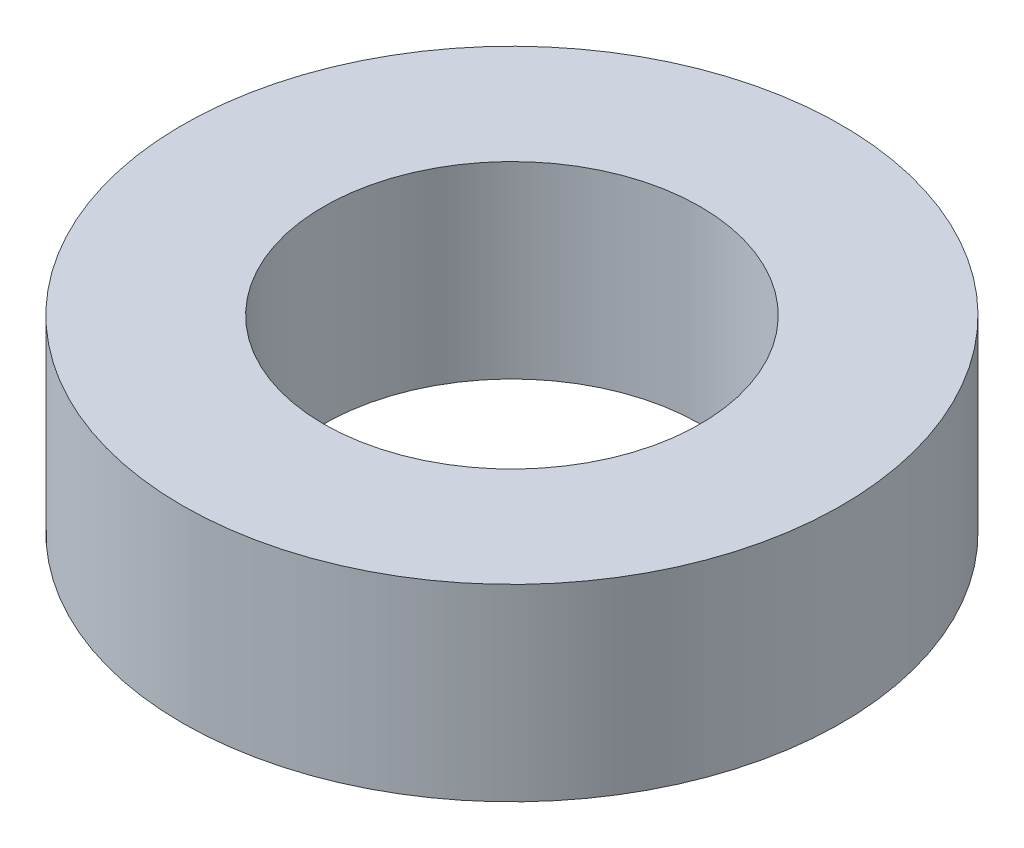
SolidWorks part; units mm, degrees
ref_plane "Front Plane" through (0, 0, 0) normal (0, 0, 1) x (1, 0, 0)
ref_plane "Top Plane" through (0, 0, 0) normal (0, 1, 0) x (1, 0, 0)
ref_plane "Right Plane" through (0, 0, 0) normal (1, 0, 0) x (0, 0, -1)
sketch "Sketch1" plane through (0, 0, 0) normal (0, 1, 0) x (1, 0, 0)
  circle A0 centre (0, 0) radius 35
  dimension "FLANGE_OD" = 70
extrude "Boss-Extrude1" add sketch "Sketch1" along normal blind 20
sketch "Sketch2" plane through (0, 0, 0) normal (0, 1, 0) x (1, 0, 0)
  circle A0 centre (0, 0) radius 20
  dimension "BORE_D" = 40
extrude "Cut-Extrude1" cut sketch "Sketch2" along normal through all
sketch "Sketch3" plane through (0, 20, 0) normal (0, 1, 0) x (1, 0, 0)
  circle A0 centre (0, 0) radius 11.385 construction
  circle A1 centre (-11.385, 0) radius 1.7165
  dimension "BOLT_D" = 3.4329
  dimension "BOLT_PCD" = 22.77
extrude "Cut-Extrude2" cut sketch "Sketch3" against normal blind 13.2263 rebuild error yes
pattern_circular "CirPattern1" count 5 over 360 rebuild error yes
